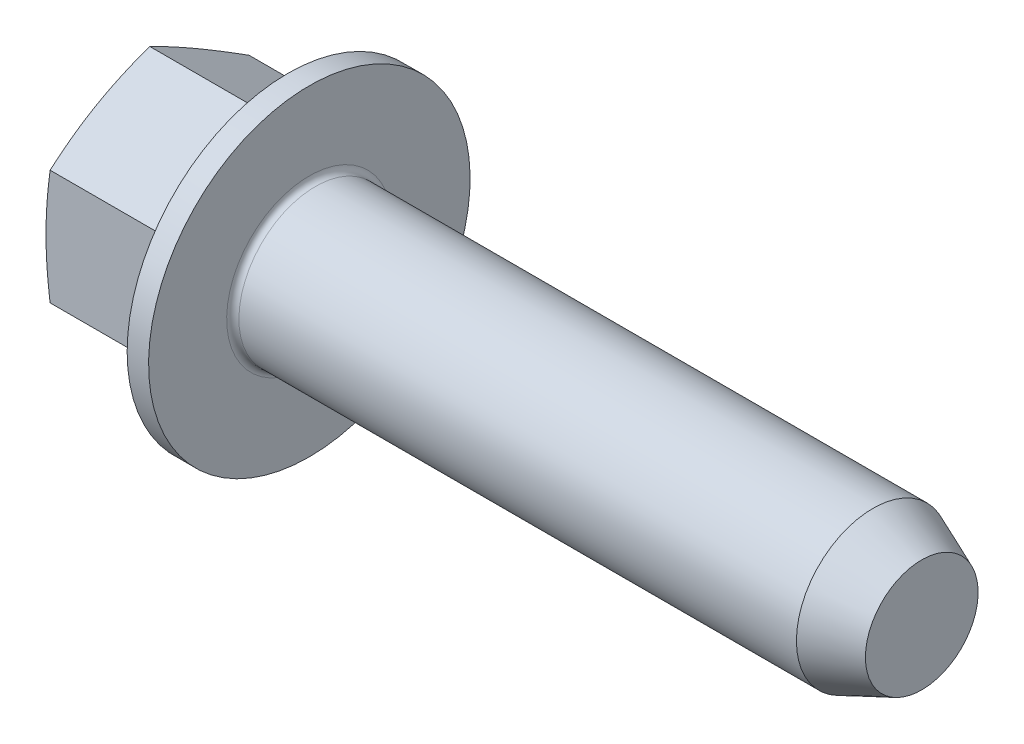
SolidWorks part; units mm, degrees
ref_plane "Front Plane" through (0, 0, 0) normal (0, 0, 1) x (1, 0, 0)
ref_plane "Top Plane" through (0, 0, 0) normal (0, 1, 0) x (1, 0, 0)
ref_plane "Right Plane" through (0, 0, 0) normal (1, 0, 0) x (0, 0, -1)
other "Configuration Table"
sketch "Sketch1" plane through (0, 0, 0) normal (0, 0, 1) x (1, 0, 0)
  line L0 (0, 0) -> (40, 0) construction
  line L1 (0, 0) -> (-10.7, 0) construction
  line L2 (0.4, 5) -> (39.172, 5)
  line L3 (40, 0) -> (40, 4.172)
  line L4 (0, 5.4) -> (0, 10.5)
  line L5 (0, 10.5) -> (-1.4, 10.5)
  line L6 (-1.4, 10.5) -> (-2.4718, 6.5)
  line L7 (-2.4718, 6.5) -> (-10.7, 6.5)
  line L8 (-10.7, 6.5) -> (-10.7, 5.2)
  line L9 (-10.7, 5.2) -> (-9.3625, 5.2)
  line L10 (-9.3625, 5.2) -> (-9.3625, 0)
  line L11 (-9.3625, 0) -> (40, 0)
  line L12 (-9.3625, 0) -> (-9.3625, 5.58) construction
  line L14 (40, 4.172) -> (39.172, 5)
  line L15 (40, 0) -> (1.5, 0) construction
  arc A0 (0.4, 5) -> (0, 5.4) centre (0.4, 5.4) cw
  dimension "D7" = 0.4
  dimension "L" = 40
  dimension "K" = 10.7
  dimension "s" = 13
  dimension "dia" = 10
  dimension "D1" = 10.4
  dimension "D2" = 1.3375
  dimension "c" = 1.4
  dimension "D4" = 15
  dimension "D5" = 45
  dimension "min" = 8.344
  dimension "B" = 38.5
  dimension "Dc" = 21
revolve "Revolve1" add sketch "Sketch1" angle 360 about L11
cosmetic thread "Cosmetic Thread1" [suppressed] parameters "D1"=37.272, "D2"=8.344
sketch "Sketch2" plane through (-10.7, 0, 0) normal (-1, 0, 0) x (0, 0, 1)
  line L1 (0, 7.5056) -> (-6.5, 3.7528)
  line L2 (-6.5, 3.7528) -> (-6.5, -3.7528)
  line L3 (-6.5, -3.7528) -> (0, -7.5056)
  line L4 (0, -7.5056) -> (6.5, -3.7528)
  line L5 (6.5, -3.7528) -> (6.5, 3.7528)
  line L6 (6.5, 3.7528) -> (0, 7.5056)
  circle A0 centre (0, 0) radius 5.2 construction
  circle A1 centre (0, 0) radius 5.2
  circle A2 centre (0, 0) radius 6.5 construction
  circle A3 centre (0, 0) radius 6.5 construction
extrude "Extrude1" add sketch "Sketch2" against normal up to next (10.7 mm away)
sketch "Sketch3" plane through (0, 0, 0) normal (0, 1, 0) x (1, 0, 0)
  line L0 (-11.5708, 3.25) -> (-9.8292, 9.75)
  line L1 (-10.7, 0) -> (-10.7, 6.5) construction
  line L2 (0, 0) -> (-3.6033, 0) construction
  line L3 (-9.8292, 9.75) -> (-11.5708, 9.75)
  line L4 (-11.5708, 9.75) -> (-11.5708, 3.25)
  dimension "D1" = 15
  dimension "D2" = 6.5
revolve "Cut-Revolve1" cut sketch "Sketch3" angle 360 about L2
fillet "Fillet1" radius 0.6 6 edges
sketch "Sketch4" plane through (0, 0, 0) normal (0, 0, 1) x (1, 0, 0)
  line L0 (0, 0) -> (5.3731, 0) construction
  line L1 (40, -4.172) -> (40, 4.172) construction
  line L3 (40, 3.68) -> (36.8132, 5)
  line L4 (0.4, 5) -> (39.172, 5) construction
  line L5 (36.8132, 5) -> (36.8132, 5.5)
  line L6 (36.8132, 5.5) -> (40, 5.5)
  line L7 (40, 5.5) -> (40, 3.68)
  dimension "D1" = 0.5
  dimension "D2" = 22.5
  dimension "Dp" = 7.36
revolve "Cut-Revolve2" cut sketch "Sketch4" angle 360 about L0
sketch "Sketch5" plane through (0, 0, 0) normal (0, 0, 1) x (1, 0, 0)
  line L0 (40, 0) -> (2.728, 0) construction
  line L1 (-9.3625, 0) -> (40, 0) construction
  line L2 (3.206, 4.172) -> (3.6841, 5)
  line L3 (3.6841, 5) -> (3.6841, 5.9561)
  line L4 (3.6841, 5.9561) -> (2.728, 5.9561)
  line L5 (2.728, 5.9561) -> (2.728, 5)
  line L6 (2.728, 5) -> (3.206, 4.172)
  dimension "B" = 37.272
  dimension "D1" = 8.344
  dimension "D2" = 10
revolve "Cut-Revolve10" [suppressed] cut sketch "Sketch5" angle 360 about L0
pattern_linear "LPattern10" [suppressed] count 25 spacing 1.5 along (1, 0, 0) of bodies 111
equation "\"D1@Sketch1\" = \"s@Sketch1\" / 10 * 8"
equation "\"D2@Sketch1\" = \"K@Sketch1\" / 8"
equation "\"D2@Sketch3\" = \"s@Sketch1\" / 2"
equation "\"D2@Cosmetic Thread1\" = \"min@Sketch1\""
equation "\"D1@Cosmetic Thread1\" = \"B@Sketch1\" -  ( \"dia@Sketch1\" - \"min@Sketch1\" )  / 2 - \"D7@Sketch1\""
equation "\"D1@Sketch5\" = \"D2@Cosmetic Thread1\""
equation "\"D2@Sketch5\" = \"dia@Sketch1\""
equation "\"B@Sketch5\" = \"D1@Cosmetic Thread1\""
equation "\"D1@LPattern10\" = int( \"D1@Cosmetic Thread1\" / \"D3@LPattern10\" + 0.999 ) "
